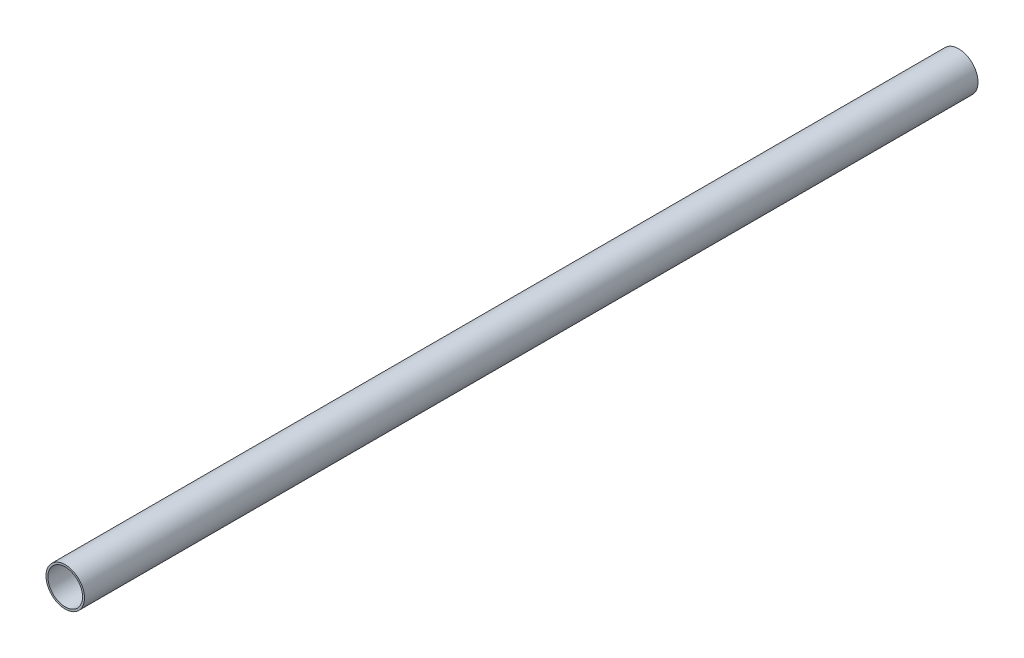
SolidWorks part; units mm, degrees
ref_plane "Front Plane" through (0, 0, 0) normal (0, 0, 1) x (1, 0, 0)
ref_plane "Top Plane" through (0, 0, 0) normal (0, 1, 0) x (1, 0, 0)
ref_plane "Right Plane" through (0, 0, 0) normal (1, 0, 0) x (0, 0, -1)
sketch "Sketch1" plane through (0, 0, 0) normal (0, 0, 1) x (1, 0, 0)
  circle A0 centre (0, 0) radius 15
  dimension "D1" = 30
extrude "Boss-Extrude1" add sketch "Sketch1" along normal blind 696.02
sketch "Sketch2" plane through (0, 0, 0) normal (0, 0, -1) x (-1, 0, 0)
  circle A0 centre (0, 0) radius 13.5
  dimension "D1" = 27
extrude "Cut-Extrude1" cut sketch "Sketch2" against normal through all
